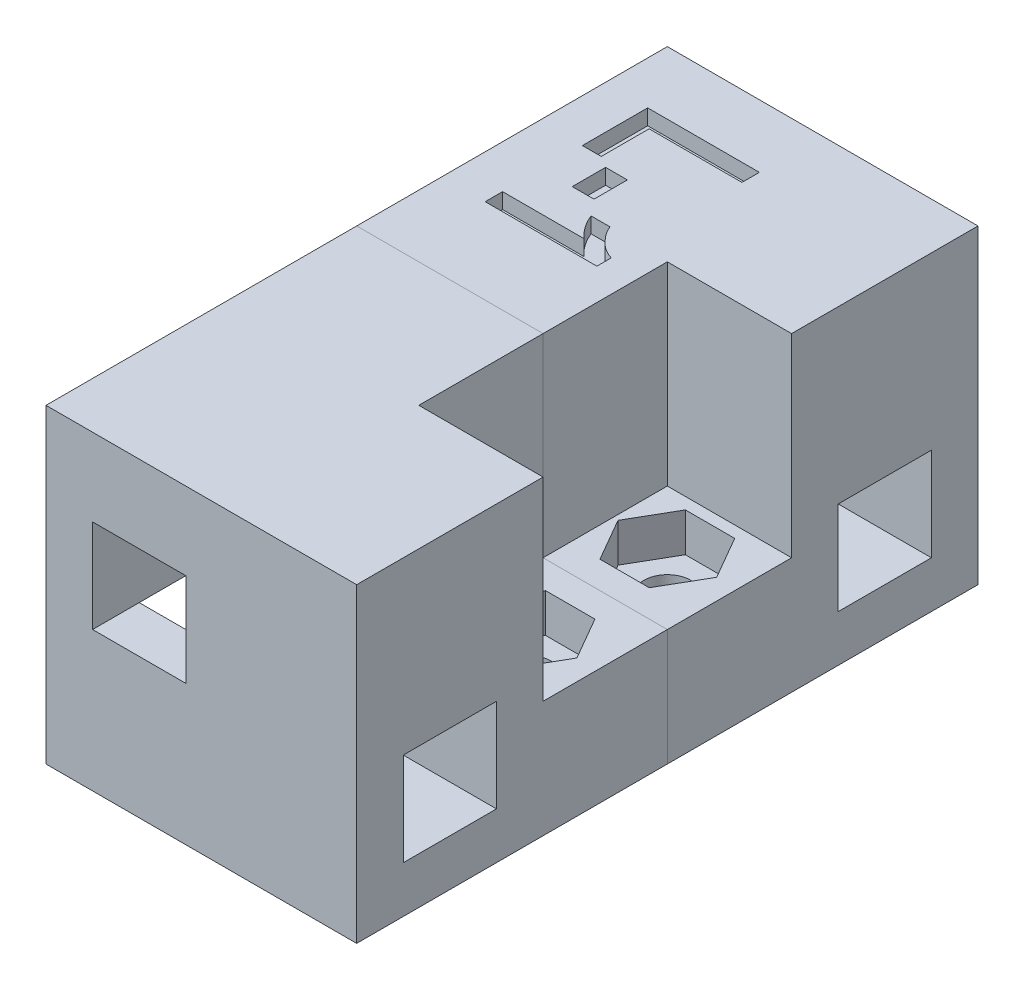
SolidWorks part; units mm, degrees
ref_plane "Plano frontal" through (0, 0, 0) normal (0, 0, 1) x (1, 0, 0)
ref_plane "Plano superior" through (0, 0, 0) normal (0, 1, 0) x (1, 0, 0)
ref_plane "Plano direito" through (0, 0, 0) normal (1, 0, 0) x (0, 0, -1)
sketch "Esboço1" plane through (0, 0, 0) normal (0, 1, 0) x (1, 0, 0)
  line L0 (12, 20) -> (20, 20)
  line L1 (0, 0) -> (20, 0)
  line L2 (0, 0) -> (0, 12)
  line L3 (0, 12) -> (20, 12)
  line L4 (20, 0) -> (20, 12)
  line L5 (0, 0) -> (12, 0)
  line L6 (0, 0) -> (0, 20)
  line L7 (0, 20) -> (12, 20)
  line L8 (12, 0) -> (12, 20)
  line L9 (20, 20) -> (20, 12)
  dimension "D1" = 20
  dimension "D2" = 20
  dimension "D3" = 12
  dimension "D4" = 12
extrude "Ressalto-extrusão1" add sketch "Esboço1" along normal blind 20 contours L1 L8 L3 L2 | L8 L1 L4 L3 | L3 L8 L7 L6 region at (6, 0, -16) region at (6, 0, -6) region at (16, 0, -6)
sketch "Esboço2" plane through (20, 0, 0) normal (1, 0, 0) x (0, 0, -1)
  line L0 (0, 0) -> (12, 0) construction
  line L1 (3, 9) -> (9, 9)
  line L2 (3, 9) -> (3, 3)
  line L3 (3, 3) -> (9, 3)
  line L4 (9, 9) -> (9, 3)
  line L5 (6, 3) -> (6, 9) construction
  line L6 (0, 20) -> (0, 0) construction
  dimension "D1" = 3
  dimension "D2" = 6
  dimension "D3" = 6
  dimension "D4" = 3
extrude "Corte-extrusão1" cut sketch "Esboço2" against normal blind 20
sketch "Esboço3" plane through (0, 0, -20) normal (0, 0, -1) x (-1, 0, 0)
  line L0 (0, 20) -> (0, 0) construction
  line L1 (-9, 15) -> (-3, 15)
  line L2 (-9, 15) -> (-9, 9)
  line L3 (-9, 9) -> (-3, 9)
  line L4 (-3, 15) -> (-3, 9)
  line L5 (0, 0) -> (-12, 0) construction
  dimension "D1" = 6
  dimension "D2" = 6
  dimension "D3" = 3
  dimension "D4" = 9
extrude "Corte-extrusão2" cut sketch "Esboço3" against normal blind 20
extrude "Ressalto-extrusão2" add sketch "Esboço1<3>" along normal blind 7.5 contours L9 L0 L8 L3 region at (16, 0, -16)
sketch "Esboço1<3>" plane through (0, 0, 0) normal (0, 1, 0) x (1, 0, 0) same geometry as "Esboço1"
sketch "Esboço4" plane through (0, 7.5, 0) normal (0, 1, 0) x (1, 0, 0)
  line L1 (13.9123, 18.25) -> (12.3246, 15.5)
  line L2 (12.3246, 15.5) -> (13.9123, 12.75)
  line L3 (13.9123, 12.75) -> (17.0877, 12.75)
  line L4 (17.0877, 12.75) -> (18.6754, 15.5)
  line L5 (18.6754, 15.5) -> (17.0877, 18.25)
  line L6 (17.0877, 18.25) -> (13.9123, 18.25)
  line L7 (12, 20) -> (20, 20) construction
  line L8 (20, 20) -> (20, 12) construction
  circle A0 centre (15.5, 15.5) radius 2.75 construction
  circle A1 centre (15.5, 15.5) radius 1.5
  dimension "D1" = 5.5
  dimension "D4" = 3
  dimension "D2" = 4.5
  dimension "D3" = 4.5
extrude "Corte-extrusão3" cut sketch "Esboço4" against normal blind 2.5 contours L4 L5 L6 L1 L2 L3
extrude "Corte-extrusão4" cut sketch "Esboço4<3>" against normal through all contours A1 region at (15.5, 7.5, -15.5)
sketch "Esboço4<3>" plane through (0, 7.5, 0) normal (0, 1, 0) x (1, 0, 0) same geometry as "Esboço4"
sketch "Esboço6" plane through (0, 20, 0) normal (0, 1, 0) x (1, 0, 0)
  line L0 (3.0821, 17.249) -> (3.0821, 2.0689) construction
  text T0 "<b>R-1</b>" font "Arial Narrow" height in points 28
extrude "R1" [suppressed] cut sketch "Esboço6" against normal blind 1
mirror "Espelhar1" about plane through (-12.1414, 20, -20) normal (0, 0, -1) of bodies 106
sketch "Esboço7" plane through (0, 20, 0) normal (0, 1, 0) x (1, 0, 0)
  line L0 (2.7834, 36.6045) -> (2.7834, 22.6702) construction
  text T0 "<b>L-1</b>" font "Arial Narrow" height in points 28
extrude "Corte-extrusão5" cut sketch "Esboço7" against normal blind 1
mirror "Espelhar2" [suppressed] of bodies 107 106
sketch "Esboço8" [suppressed] plane through (0, 20, 0) normal (0, 1, 0) x (1, 0, 0)
  line L0 (29.9996, 17.2964) -> (29.9996, 3.0003) construction
  text T0 "<b>R-2</b>" font "Arial Narrow" height in points 28
extrude "Corte-extrusão6" [suppressed] cut sketch "Esboço8" against normal blind 1
sketch "Esboço9" [suppressed] plane through (0, 20, 0) normal (0, 1, 0) x (1, 0, 0)
  line L1 (0, 40) -> (20, 40)
  line L2 (0, 40) -> (0, 20)
  line L3 (0, 20) -> (20, 20)
  line L4 (20, 40) -> (20, 20)
extrude "Corte-extrusão7" [suppressed] cut sketch "Esboço9" against normal blind 25
move or copy body "Corpo-Mover/Copiar1" [suppressed] bodies to move or copy 107 110
